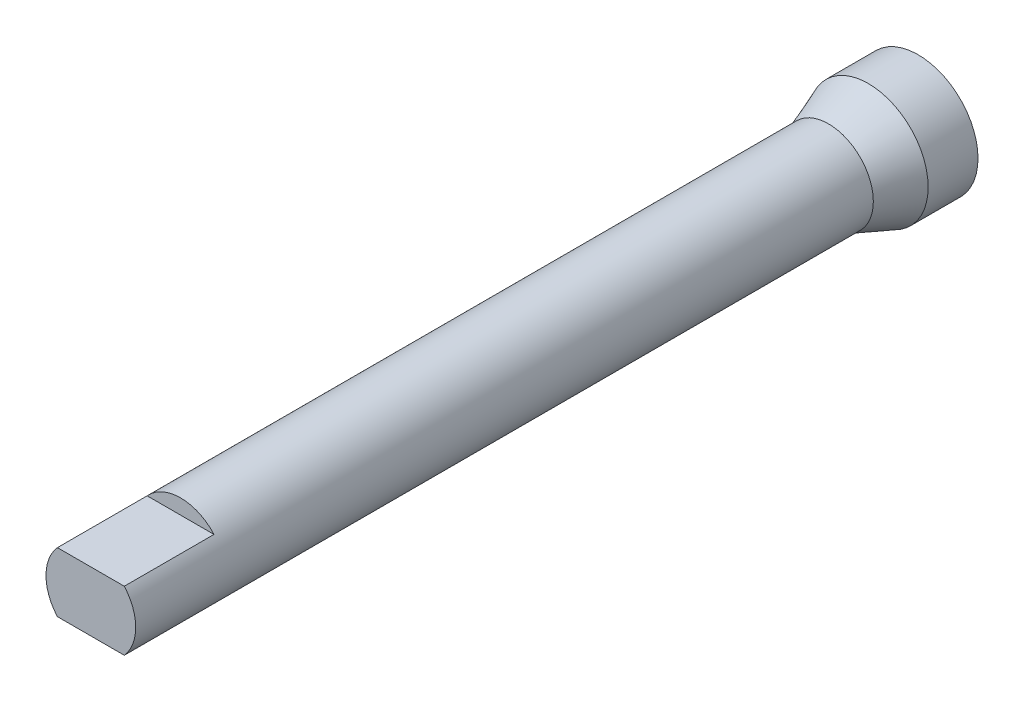
SolidWorks part; units mm, degrees
ref_plane "Front Plane" through (0, 0, 0) normal (0, 0, 1) x (1, 0, 0)
ref_plane "Top Plane" through (0, 0, 0) normal (0, 1, 0) x (1, 0, 0)
ref_plane "Right Plane" through (0, 0, 0) normal (1, 0, 0) x (0, 0, -1)
sketch "Sketch2" plane through (0, 0, 0) normal (0, 1, 0) x (1, 0, 0)
  line L0 (-30, 0) -> (0, 0) construction
  line L1 (-30, 0) -> (-30, -25)
  line L2 (-30, -25) -> (-22.5, -45)
  line L3 (-30, 0) -> (-25, 0)
  line L4 (-25, 0) -> (-25, -25)
  line L5 (-25, -25) -> (-17.5, -45)
  line L6 (-17.5, -45) -> (-22.5, -45)
  dimension "D1" = 30
  dimension "D2" = 20
  dimension "D3" = 25
  dimension "D4" = 22.5
  dimension "D5" = 5
  dimension "D6" = 5
  dimension "D7" = 5
ref_axis "Axis1" through (0, 0, 47.25) along (0, 0, -1)
revolve "Revolve1" add sketch "Sketch2" angle 360 about axis through (0, 0, 47.25) along (0, 0, -1)
sketch "Sketch3" plane through (0, 0, 45) normal (0, 0, 1) x (1, 0, 0)
  circle A0 centre (0, 0) radius 17.5 construction
  circle A1 centre (0, 0) radius 22.5 construction
  circle A2 centre (0, 0) radius 17.5
  circle A3 centre (0, 0) radius 22.5
extrude "Boss-Extrude1" add sketch "Sketch3" along normal blind 320
sketch "Sketch4" plane through (0, 0, 365) normal (0, 0, 1) x (1, 0, 0)
  circle A0 centre (0, 0) radius 22.5 construction
  circle A1 centre (0, 0) radius 22.5
extrude "Boss-Extrude2" add sketch "Sketch4" along normal blind 50
sketch "Sketch5" plane through (0, 0, 415) normal (0, 0, 1) x (1, 0, 0)
  line L0 (-50, 15) -> (50, 15) construction
  line L1 (50, 15) -> (50, -15) construction
  line L2 (50, -15) -> (-50, -15) construction
  line L3 (-50, -15) -> (-50, 15) construction
  line L4 (-50, 15) -> (50, -15) construction
  line L5 (-50, -15) -> (50, 15) construction
  line L6 (24.75, 0) -> (-24.75, 0) construction
  line L7 (16.7705, 15) -> (-16.7705, 15)
  line L8 (16.7705, 15) -> (16.7705, 35)
  line L9 (16.7705, 35) -> (-16.7705, 35)
  line L10 (-16.7705, 15) -> (-16.7705, 35)
  line L11 (16.7705, -35) -> (-16.7705, -35)
  line L12 (-16.7705, -15) -> (-16.7705, -35)
  line L13 (16.7705, -15) -> (-16.7705, -15)
  line L14 (16.7705, -15) -> (16.7705, -35)
  circle A0 centre (0, 0) radius 22.5 construction
  circle A1 centre (0, 0) radius 22.5 construction
  point P2 (0, 0)
  dimension "D1" = 30
  dimension "D2" = 100
extrude "Cut-Extrude1" cut sketch "Sketch5" against normal blind 45
equation "\"wideTopWidth\"= 60mm"
equation "\"D1@Sketch2\"=\"wideTopWidth\"/2"
equation "\"tubeWidth\"= 45mm"
equation "\"wallThickness\"= 5mm"
equation "\"D4@Sketch2\"=\"tubeWidth\"/2"
equation "\"D5@Sketch2\"=\"wallThickness\""
equation "\"D7@Sketch2\"=\"wallThickness\""
equation "\"D6@Sketch2\"=\"wallThickness\""
equation "\"tubeFullLen\"= 370mm"
equation "\"D1@Boss-Extrude1\"=\"tubeFullLen\"-50"
equation "\"D1@Boss-Extrude2\"=50"
